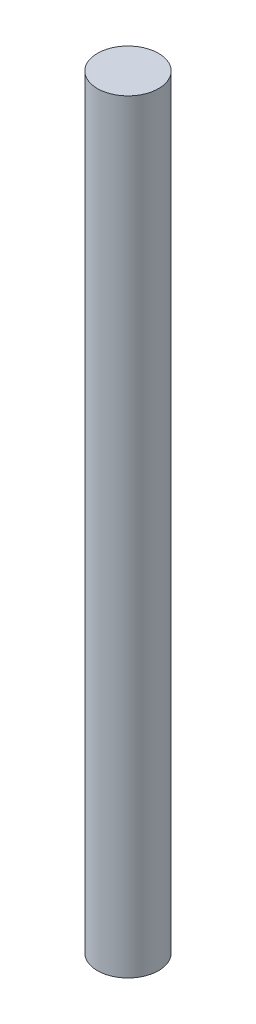
SolidWorks part; units mm, degrees
material "Brass"
ref_plane "Front Plane" through (0, 0, 0) normal (0, 0, 1) x (1, 0, 0)
ref_plane "Top Plane" through (0, 0, 0) normal (0, 1, 0) x (1, 0, 0)
ref_plane "Right Plane" through (0, 0, 0) normal (1, 0, 0) x (0, 0, -1)
sketch "Sketch1" plane through (0, 0, 0) normal (0, 1, 0) x (1, 0, 0)
  circle A0 centre (0, 0) radius 0.5
  dimension "D1" = 1
extrude "Boss-Extrude1" add sketch "Sketch1" along normal blind 12.5
scale "Scale1" scale about centroid uniform scaling yes scale factor 6
